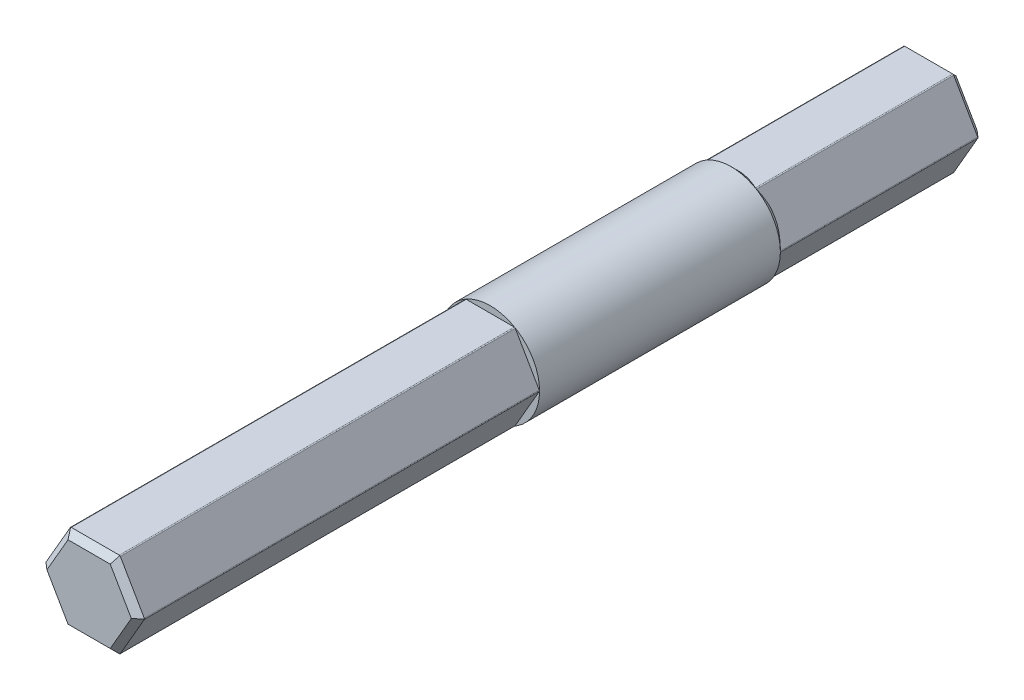
SolidWorks part; units mm, degrees
material "PETG"
ref_plane "Front Plane" through (0, 0, 0) normal (0, 0, 1) x (1, 0, 0)
ref_plane "Top Plane" through (0, 0, 0) normal (0, 1, 0) x (1, 0, 0)
ref_plane "Right Plane" through (0, 0, 0) normal (1, 0, 0) x (0, 0, -1)
sketch "Sketch1" plane through (0, 0, 0) normal (0, 0, 1) x (1, 0, 0)
  circle A0 centre (0, 0) radius 3.99
  dimension "Shaft Dia" = 7.98
extrude "Boss-Extrude1" add sketch "Sketch1" along normal blind 20
sketch "Sketch2" plane through (0, 0, 20) normal (0, 0, 1) x (1, 0, 0)
  line L1 (4, 0) -> (2, 3.4641) construction
  line L2 (2, 3.4641) -> (-2, 3.4641) construction
  line L3 (-2, 3.4641) -> (-4, 0) construction
  line L4 (-4, 0) -> (-2, -3.4641) construction
  line L5 (-2, -3.4641) -> (2, -3.4641) construction
  line L6 (2, -3.4641) -> (4, 0) construction
  line L7 (3.9942, 0) -> (1.9971, 3.4591)
  line L8 (1.9971, 3.4591) -> (-1.9971, 3.4591)
  line L9 (-1.9971, 3.4591) -> (-3.9942, 0)
  line L10 (-3.9942, 0) -> (-1.9971, -3.4591)
  line L11 (-1.9971, -3.4591) -> (1.9971, -3.4591)
  line L12 (1.9971, -3.4591) -> (3.9942, 0)
  circle A0 centre (0, 0) radius 3.4641 construction
  circle A1 centre (0, 0) radius 3.4591 construction
  dimension "Hex Circumscribed Nominal Dia" = 8
  dimension "Hex Flat To Flat Offset" = 0.005
extrude "Boss-Extrude2" add sketch "Sketch2" along normal blind 32.48
sketch "Sketch3" plane through (0, 0, 0) normal (0, 0, -1) x (-1, 0, 0)
  line L0 (-1.9971, 3.4591) -> (-1.9886, 3.4591) construction
  line L13 (3.9942, 0) -> (1.9971, 3.4591)
  line L14 (1.9971, 3.4591) -> (-1.9971, 3.4591)
  line L15 (-1.9971, 3.4591) -> (-3.9942, 0)
  line L16 (-3.9942, 0) -> (-1.9971, -3.4591)
  line L17 (-1.9971, -3.4591) -> (1.9971, -3.4591)
  line L18 (1.9971, -3.4591) -> (3.9942, 0)
  circle A1 centre (0, 0) radius 3.4591 construction
extrude "Boss-Extrude3" add sketch "Sketch3" along normal blind 16
chamfer "Chamfer1" distance 0.5 angle 45 12 edges at (0, -3.4591, 52.48) (-2.9957, -1.7296, 52.48) (-2.9957, 1.7296, 52.48) (0, 3.4591, 52.48) (2.9957, 1.7296, 52.48) (2.9957, -1.7296, 52.48) (0, -3.4591, -16) (2.9957, -1.7296, -16) (2.9957, 1.7296, -16) (0, 3.4591, -16) (-2.9957, 1.7296, -16) (-2.9957, -1.7296, -16)
fillet "Fillet1" radius 0.1 12 edges at (-1.9971, 3.4591, -7.75) (-3.9942, 0, -7.75) (1.9971, 3.4591, -7.75) (3.9942, 0, -7.75) (1.9971, -3.4591, -7.75) (-1.9971, -3.4591, -7.75) (1.9971, -3.4591, 35.99) (-1.9971, -3.4591, 35.99) (-3.9942, 0, 35.99) (-1.9971, 3.4591, 35.99) (3.9942, 0, 35.99) (1.9971, 3.4591, 35.99)
chamfer "Chamfer2" distance 0.5 angle 45 1 edges at (3.99, 0, 0)
equation "\"tol_dia_id_intfc\" = 0.0200mm ' For hole diameters - Interference fit"
equation "\"tol_dia_id_slip\"  = 0.0300mm ' For hole diameters - Slip fit"
equation "\"tol_dia_id_clear\" = 0.0500mm ' For hole diameters - Clearance fit"
equation "\"tol_dia_od_intfc\" = 0.0200mm ' For shaft diameters - Interference fit"
equation "\"tol_dia_od_slip\"  = 0.0300mm ' For shaft diameters - Slip fit"
equation "\"tol_dia_od_clear\" = 0.0500mm ' For shaft diameters - Clearance fit"
equation "\"tol_general_intfc\"= 0.0030mm ' For general parts (Horiz) - Interference fit"
equation "\"tol_general_slip\" = 0.0050mm ' For general parts (Horiz) - Slip fit"
equation "\"tol_general_clear\"= 0.0100mm ' For general parts (Horiz) - Clearance fit"
equation "\"tol_layer_intfc\"  = 0.0030mm ' For all parts (Vert) - Interference fit"
equation "\"tol_layer_slip\"   = 0.0050mm ' For all parts (Vert) - Slip fit"
equation "\"tol_layer_clear\"  = 0.0100mm ' For all parts (Vert) - Clearance fit"
equation "\"tol_corner_rad\"   = 0.100mm ' For corners that fit into other parts"
equation "\"Shaft Dia@Sketch1\" = \"nominal_dia\" - \"tol_dia_od_intfc\""
equation "\"nominal_dia\"= 8.00mm"
equation "\"Hex Circumscribed Nominal Dia@Sketch2\" = \"nominal_dia\""
equation "\"Hex Flat To Flat Offset@Sketch2\"=\"tol_general_slip\""
equation "\"D1@Fillet1\"=\"tol_corner_rad\""
equation "\"D1@Boss-Extrude2\"=32.50mm-\"tol_layer_clear\"*2"
